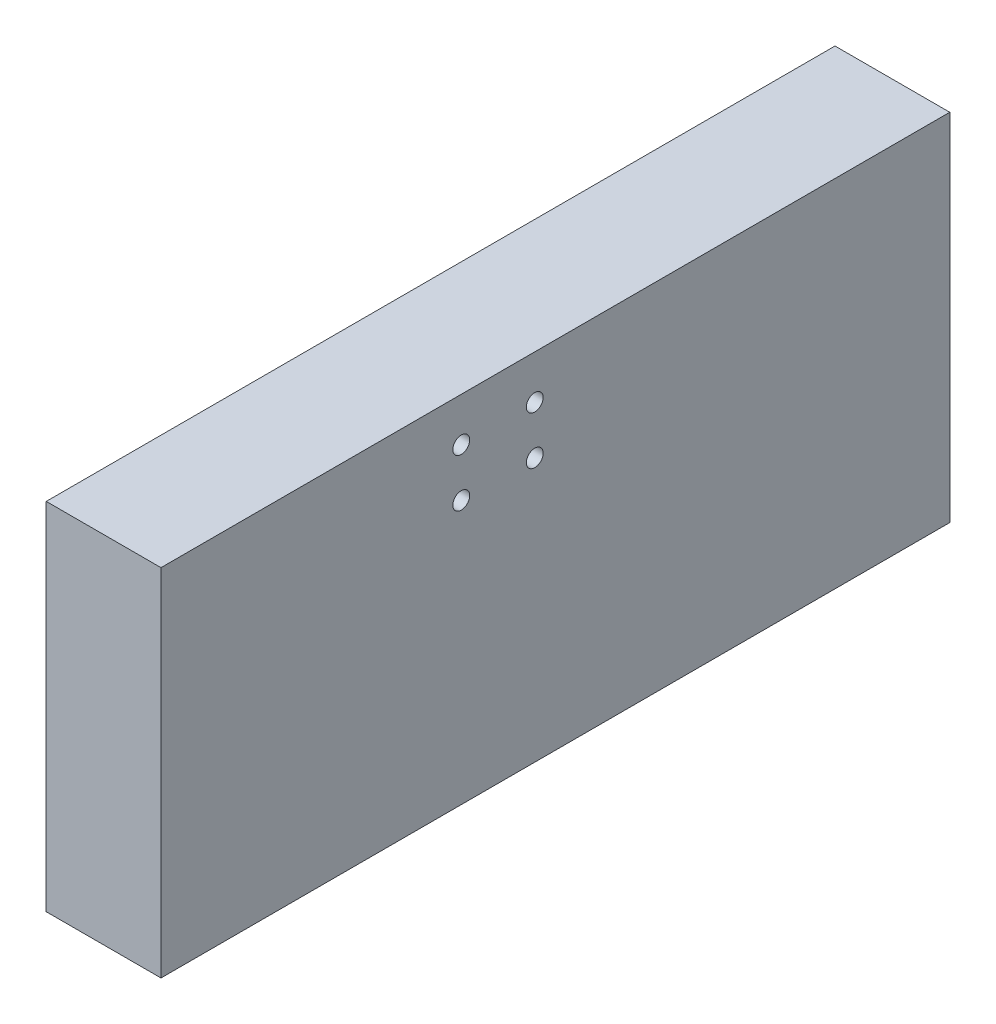
SolidWorks part; units mm, degrees
ref_plane "Front" through (0, 0, 0) normal (0, 0, 1) x (1, 0, 0)
ref_plane "Top" through (0, 0, 0) normal (0, 1, 0) x (1, 0, 0)
ref_plane "Right" through (0, 0, 0) normal (1, 0, 0) x (0, 0, -1)
sketch "Sketch1" plane through (0, 0, 0) normal (0, 1, 0) x (1, 0, 0)
  line L1 (-75, -75) -> (75, -75)
  line L2 (-75, -75) -> (-75, 75)
  line L3 (-75, 75) -> (75, 75)
  line L4 (75, -75) -> (75, 75)
  line L5 (-75, -75) -> (75, 75) construction
  line L6 (-75, 75) -> (75, -75) construction
  point P0 (0, 0)
  dimension "D1" = 150
  dimension "D2" = 150
extrude "Boss-Extrude1" add sketch "Sketch1" against normal blind 59
sketch "Sketch2" plane through (0, 0, 0) normal (0, 1, 0) x (1, 0, 0)
  line L1 (-55.95, -55.95) -> (55.95, -55.95)
  line L2 (-55.95, -55.95) -> (-55.95, 55.95)
  line L3 (-55.95, 55.95) -> (55.95, 55.95)
  line L4 (55.95, -55.95) -> (55.95, 55.95)
  line L5 (-55.95, -55.95) -> (55.95, 55.95) construction
  line L6 (-55.95, 55.95) -> (55.95, -55.95) construction
  point P0 (0, 0)
  dimension "D1" = 111.9
  dimension "D2" = 111.9
extrude "Cut-Extrude1" cut sketch "Sketch2" against normal through all
ref_axis "Axis1" through (0, 0, 0) along (0, -1, 0)
sketch "Sketch9" plane through (-75, 0, 0) normal (-1, 0, 0) x (0, 0, 1)
  line L0 (-75, 0) -> (75, 0) construction
  line L1 (0, 0) -> (7.5, 0)
  line L7 (0, 0) -> (-7.5, 0)
  circle A0 centre (-6.1, -7.25) radius 1.4
  circle A1 centre (6.1, -7.25) radius 1.4
  circle A2 centre (6.1, -15.25) radius 1.4
  circle A3 centre (-6.1, -15.25) radius 1.4
  dimension "D4" = 2.8
  dimension "D2" = 7.5
  dimension "D3" = 7.5
  dimension "D5" = 7.25
extrude "Cut-Extrude4" cut sketch "Sketch9" against normal blind 20 contours A0 | A1 | A2 | A3 region at (-75, -7.25, -6.1)
pattern_circular "CirPattern1" count 3 every 90 about axis through (0, 0, 0) along (0, -1, 0) of "Cut-Extrude4" reverse direction yes
sketch "Sketch10" plane through (0, 0, 0) normal (0, 1, 0) x (1, 0, 0)
  line L0 (-55.95, 55.95) -> (55.95, 55.95)
  line L1 (-55.95, 55.95) -> (-55.95, 161.3983)
  line L2 (55.95, 55.95) -> (55.95, 161.3983)
  line L3 (-55.95, 161.3983) -> (55.95, 161.3983)
extrude "Cut-Extrude6" cut sketch "Sketch10" against normal through all
sketch "Sketch11" plane through (0, 0, 0) normal (0, 1, 0) x (1, 0, 0)
  line L0 (-75, 75) -> (-75, -75) construction
  line L1 (-55.95, 75) -> (75, 75)
  line L2 (-55.95, 75) -> (-55.95, -75)
  line L3 (-55.95, -75) -> (75, -75)
  line L4 (75, 75) -> (75, -75)
  line L5 (-55.95, -75) -> (-75, -75)
  line L6 (-55.95, -75) -> (-55.95, -55.95)
  line L7 (-55.95, -55.95) -> (-75, -55.95)
  line L8 (-75, -75) -> (-75, -55.95)
extrude "Cut-Extrude7" cut sketch "Sketch11" against normal through all contours L1 L7 L6 | L7 L2 L0 L5 L6 | L2 L7 L3 region at (-65.475, 0, 65.475) region at (9.525, 0, 0)
